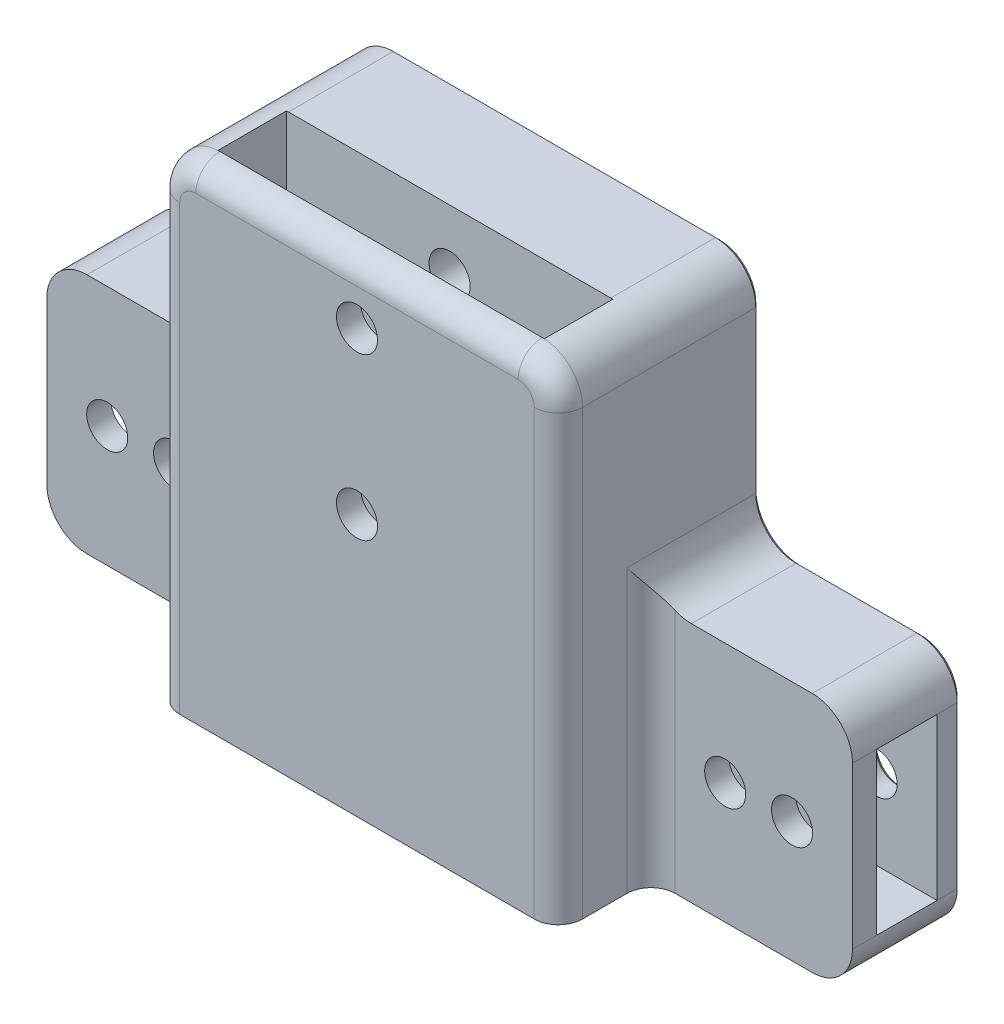
SolidWorks part; units mm, degrees
material "PET"
ref_plane "Front Plane" through (0, 0, 0) normal (0, 0, 1) x (1, 0, 0)
ref_plane "Top Plane" through (0, 0, 0) normal (0, 1, 0) x (1, 0, 0)
ref_plane "Right Plane" through (0, 0, 0) normal (1, 0, 0) x (0, 0, -1)
sketch "Sketch1" plane through (0, 0, 0) normal (0, 0, 1) x (1, 0, 0)
  line L0 (0, 46.5105) -> (0, -31.701) construction
  line L1 (25, -30) -> (0, -30)
  line L2 (25, 0) -> (25, 30)
  line L3 (25, 30) -> (0, 30)
  line L4 (0, -30) -> (0, 30)
  line L5 (25, -30) -> (0, 30) construction
  line L6 (25, 30) -> (0, -30) construction
  line L7 (25, -30) -> (25, 0) construction
  line L8 (50, 0) -> (25, 0)
  line L9 (50, 0) -> (50, -30)
  line L10 (50, -30) -> (25, -30)
  line L12 (50, 0) -> (25, -30) construction
  line L13 (50, -30) -> (25, 0) construction
  point P0 (12.5, 0)
  point P9 (37.5, -15)
  dimension "D1" = 50
  dimension "D2" = 60
  dimension "D3" = 100
  dimension "D4" = 30
extrude "Boss-Extrude1" add sketch "Sketch1" along normal mid plane 25
sketch "Sketch3" plane through (0, 0, 0) normal (0, 1, 0) x (1, 0, 0)
  line L0 (25, -12.5) -> (25, 12.5) construction
  line L1 (50, -12.5) -> (25, -12.5)
  line L2 (50, -12.5) -> (50, -1)
  line L3 (50, -1) -> (25, -1)
  line L4 (25, -12.5) -> (25, -1)
  line L5 (50, 12.5) -> (25, 12.5) construction
  dimension "D1" = 13.5
extrude "Cut-Extrude2" cut sketch "Sketch3" against normal through all
sketch "Sketch2" plane through (0, 0, 0) normal (0, 1, 0) x (1, 0, 0)
  line L0 (0, 16.2768) -> (0, -14.689) construction
  line L6 (0, -9.5) -> (20.25, -9.5)
  line L7 (0, -9.5) -> (0, -1)
  line L8 (0, -1) -> (20.25, -1)
  line L9 (20.25, -9.5) -> (20.25, -1)
  line L10 (25, -12.5) -> (0, -12.5) construction
  dimension "D1" = 40.5
  dimension "D2" = 8.5
  dimension "D3" = 3
extrude "Cut-Extrude1" cut sketch "Sketch2" against normal through all both and the other way through all
sketch "Sketch4" plane through (50, 0, 0) normal (1, 0, 0) x (0, 0, -1)
  line L0 (12.5, -30) -> (12.5, 0) construction
  line L1 (2, -25) -> (9.5, -25)
  line L2 (2, -25) -> (2, -5)
  line L3 (2, -5) -> (9.5, -5)
  line L4 (9.5, -25) -> (9.5, -5)
  line L5 (2, -25) -> (9.5, -5) construction
  line L6 (2, -5) -> (9.5, -25) construction
  line L7 (-1, -30) -> (12.5, -30) construction
  point P0 (5.75, -15)
  point P8 (12.5, -15)
  point P11 (5.75, -30)
  dimension "D1" = 20
  dimension "D2" = 7.5
extrude "Cut-Extrude3" cut sketch "Sketch4" against normal through all
mirror "Mirror1" about plane through (0, 0, 0) normal (1, 0, 0) of bodies 104
sketch "Sketch8" plane through (0, 0, 12.5) normal (0, 0, 1) x (1, 0, 0)
  line L0 (25, 30) -> (-25, 30) construction
  circle A0 centre (0, 22.5) radius 2.55
  circle A1 centre (0, 2.5) radius 2.55
  point P6 (0, 0)
  dimension "D1" = 5.1
  dimension "D2" = 20
  dimension "D3" = 7.5
extrude "Pin Hole" cut sketch "Sketch8" against normal through all
sketch "Sketch9" plane through (0, 0, -12.5) normal (0, 0, -1) x (-1, 0, 0)
  circle A0 centre (0, 22.5) radius 3.5
  circle A1 centre (0, 2.5) radius 3.5
  dimension "D1" = 7
extrude "Counterbore" cut sketch "Sketch9" against normal blind 9
sketch "Sketch7" plane through (0, 0, 1) normal (0, 0, 1) x (1, 0, 0)
  line L0 (50, -30) -> (50, 0) construction
  circle A0 centre (42.5, -15) radius 2.55
  point P4 (50, -15)
  dimension "D2" = 5.1
  dimension "D1" = 7.5
extrude "Cut-Extrude5" cut sketch "Sketch7" against normal through all
pattern_linear "LPattern1" count 2 spacing 8.3 along (-1, 0, 0) of "Cut-Extrude5"
mirror "Mirror2" about plane through (0, 0, 0) normal (1, 0, 0) of "LPattern1"
fillet "Fillet1" radius 5 8 edges at (25, 30, 0) (-25, 30, 0) (-50, 0, -5.75) (50, 0, -5.75) (-25, 0, -5.75) (25, 0, -5.75) (-50, -30, -5.75) (50, -30, -5.75)
chamfer "Chamfer1" distance 0.5 angle 45 22 edges at (0, -30, -12.5) (-23.5355, 28.5355, -12.5) (-25, 15, -12.5) (-26.4645, 1.4645, -12.5) (-37.5, 0, -12.5) (-48.5355, -1.4645, -12.5) (-50, -15, -12.5) (50, -15, -12.5) (48.5355, -1.4645, -12.5) (37.5, 0, -12.5) (26.4645, 1.4645, -12.5) (25, 15, -12.5) (23.5355, 28.5355, -12.5) (0, 30, -12.5) (-3.5, 2.5, -12.5) (-3.5, 22.5, -12.5) (45.05, -15, -12.5) (36.75, -15, -12.5) (-36.75, -15, -12.5) (-45.05, -15, -12.5) (48.5355, -28.5355, -12.5) (-48.5355, -28.5355, -12.5)
fillet "Fillet2" radius 3 7 edges at (25, -2.5, 12.5) (23.5355, 28.5355, 12.5) (0, 30, 12.5) (-23.5355, 28.5355, 12.5) (-25, -2.5, 12.5) (-25, -12.5, 1) (25, -12.5, 1)
